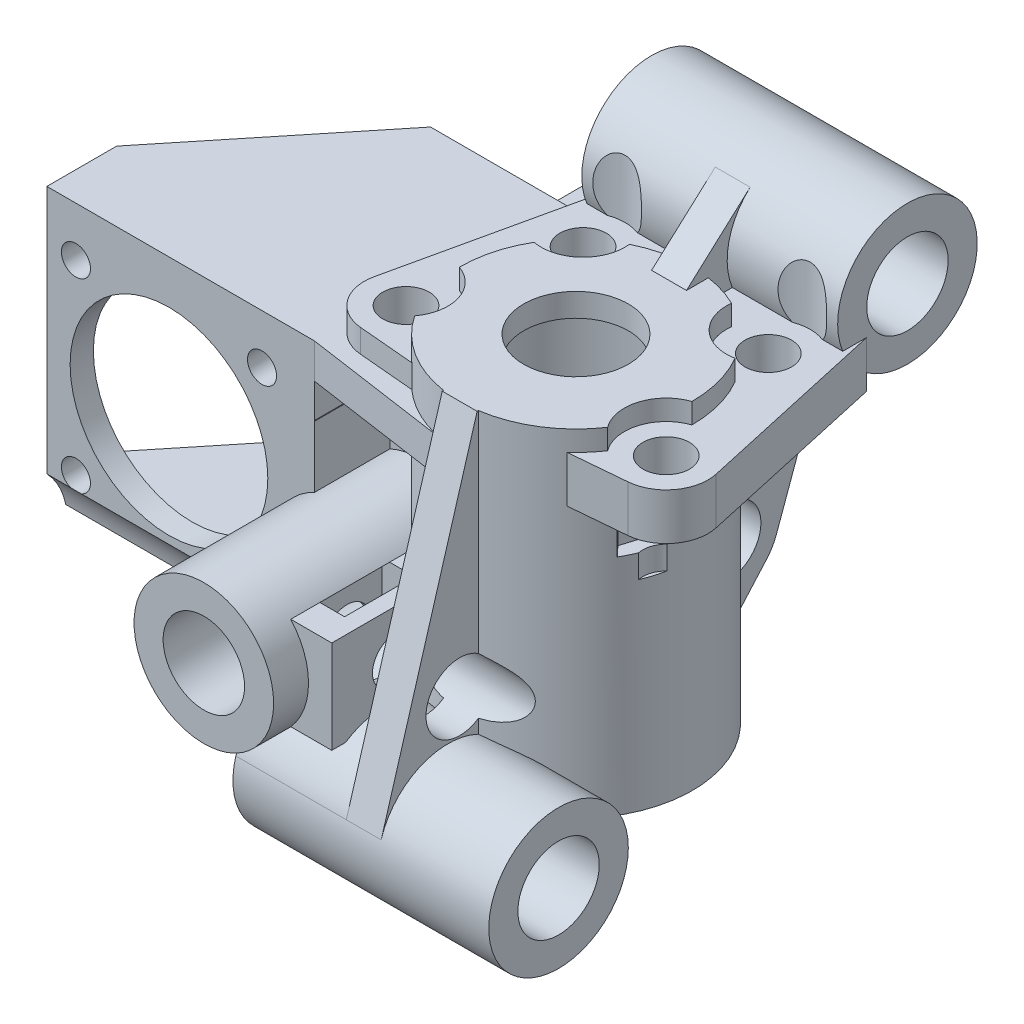
SolidWorks part; units mm, degrees
ref_plane "Front Plane" through (0, 0, 0) normal (0, 0, 1) x (1, 0, 0)
ref_plane "Top Plane" through (0, 0, 0) normal (0, 1, 0) x (1, 0, 0)
ref_plane "Right Plane" through (0, 0, 0) normal (1, 0, 0) x (0, 0, -1)
sketch "Sketch1" plane through (0, 0, 0) normal (0, 0, 1) x (1, 0, 0)
  line L0 (0, 45.2286) -> (0, -45.546) construction
  line L1 (4.5, -14.5) -> (10, -14.5)
  line L2 (10, -14.5) -> (10, 14.5)
  line L7 (10, 14.5) -> (4.5, 14.5)
  line L8 (4.5, 14.5) -> (4.5, 12.5)
  line L9 (4.5, 12.5) -> (8, 12.5)
  line L10 (8, 12.5) -> (8, -12.5)
  line L11 (8, -12.5) -> (4.5, -12.5)
  line L12 (4.5, -12.5) -> (4.5, -14.5)
  line L13 (-9.5385, 0) -> (23.7713, 0) construction
  dimension "D1" = 4.5
  dimension "D2" = 2
  dimension "D3" = 8
  dimension "D4" = 25
  dimension "D5" = 2
revolve "Revolve1" add sketch "Sketch1" angle 360 about L0
ref_axis "Bearing Axis" through (0, -14.5, 0) along (0, 1, 0)
sketch "Sketch3" plane through (0, 0, 0) normal (1, 0, 0) x (0, 0, -1)
  line L0 (6, 14.5) -> (6, -14.5) construction
  line L2 (0, -14.5) -> (0, 14.5) construction
  line L3 (10, 14.5) -> (-10, 14.5) construction
  line L4 (-10, -14.5) -> (10, -14.5) construction
  circle A0 centre (17.5, 15) radius 3.5
  circle A1 centre (17.5, 15) radius 6
  circle A2 centre (-12.5, -15) radius 3.5
  circle A3 centre (-12.5, -15) radius 6
  dimension "D1" = 7
  dimension "D2" = 12
  dimension "D3" = 6
  dimension "D4" = 30
  dimension "D5" = 30
  dimension "D6" = 11.5
  dimension "D7" = 15
extrude "Boss-Extrude2" add sketch "Sketch3" along normal mid plane 22 separate body
sketch "Sketch2" plane through (0, 0, 0) normal (0, 0, 1) x (1, 0, 0)
  circle A0 centre (-12, -6) radius 6
  circle A1 centre (-12, -6) radius 3.5
  dimension "D1" = 7
  dimension "D2" = 12
  dimension "D3" = 12
  dimension "D4" = 6
extrude "Boss-Extrude1" add sketch "Sketch2" along normal blind 20 and the other way blind 15
ref_axis "Smooth Rod Axis" through (-12, -6, -15) along (0, 0, 1)
sketch "Sketch4" plane through (0, 0, 0) normal (0, 1, 0) x (1, 0, 0)
  line L0 (-14.5, -8) -> (-37.5, -8)
  line L1 (-37.5, -8) -> (-37.5, -6)
  line L2 (-37.5, -6) -> (-16.5, -6)
  line L3 (-16.5, -6) -> (-16.5, 19)
  line L4 (-16.5, 19) -> (-14.5, 19)
  line L5 (-14.5, 19) -> (-14.5, -8)
  dimension "D1" = 2
  dimension "D2" = 2
  dimension "D3" = 21
  dimension "D4" = 25
  dimension "D5" = 6
  dimension "D6" = 1
extrude "Boss-Extrude Motor Mount" add sketch "Sketch4" along normal blind 9 and the other way blind 12
sketch "Sketch5" plane through (0, 9, 0) normal (0, 1, 0) x (1, 0, 0)
  line L0 (-14.5, -8) -> (-37.5, -8)
  line L1 (-37.5, -8) -> (-37.5, -6)
  line L2 (-37.5, -6) -> (-37.5, -2)
  line L3 (-37.5, -2) -> (-20.5, 19)
  line L4 (-16.5, 19) -> (-14.5, 19)
  line L6 (-20.5, 19) -> (-16.5, 19)
  line L7 (-14.5, -8) -> (-1.4365, -9.8963)
  line L9 (-14.5, 19) -> (4.682, 8.8362)
  line L11 (-16.5, 19) -> (-16.5, -6) construction
  arc A0 (4.682, 8.8362) -> (-1.4365, -9.8963) centre (0, 0) ccw
  circle A2 centre (0, 0) radius 10 construction
  dimension "D1" = 6
  dimension "D2" = 6
extrude "Boss-Extrude4" add sketch "Sketch5" along normal blind 1.75 and the other way blind 1.25
sketch "Sketch6" plane through (0, -12, 0) normal (0, -1, 0) x (1, 0, 0)
  line L0 (-37.5, 8) -> (-37.5, 2)
  line L1 (-37.5, 2) -> (-24.5476, -14)
  line L2 (-24.5476, -14) -> (-16.5, -14)
  line L3 (-6.9508, -15) -> (-16.5, -15)
  line L4 (-16.5, 8) -> (-37.5, 8)
  line L5 (-20.5, -19) -> (-37.5, 2) construction
  line L6 (-16.5, -15) -> (-16.5, -14)
  line L7 (-16.5, 6) -> (-37.5, 6) construction
  line L8 (-16.5, 8) -> (-1.2502, 9.9215)
  line L9 (-14.5, -15) -> (-6, -15) construction
  line L11 (4.682, -8.8362) -> (-6.9508, -15)
  line L13 (4.682, -8.8362) -> (-14.5, -19) construction
  arc A0 (-1.2502, 9.9215) -> (4.682, -8.8362) centre (0, 0) ccw
  circle A1 centre (0, 0) radius 10 construction
  dimension "D1" = 20
extrude "Boss-Extrude5" add sketch "Sketch6" along normal blind 1.75 and the other way blind 1.25
ref_plane "Flange Plane" through (0, 10.75, 0) normal (0, 1, 0) x (-1, 0, 0)
sketch "Sketch7" plane through (0, 0, 6) normal (0, 0, -1) x (-1, 0, 0)
  line L1 (37.5, 9) -> (16.5, 9)
  line L2 (37.5, 9) -> (37.5, -12)
  line L3 (37.5, -12) -> (16.5, -12)
  line L4 (16.5, 9) -> (16.5, -12)
  line L7 (37.5, 10.75) -> (14.5, 10.75) construction
  line L8 (14.5, 7.75) -> (14.5, -0.5456) construction
  line L9 (37.5, 10.75) -> (37.5, -13.75) construction
  dimension "D1" = 1.75
  dimension "D2" = 2
  dimension "D3" = 21
extrude "Cut-Extrude1" cut sketch "Sketch7" along normal blind 32
sketch "Sketch8" plane through (0, 0, 20) normal (0, 0, 1) x (1, 0, 0)
  circle A0 centre (-12, -6) radius 3.5
  circle A1 centre (-12, -6) radius 3.5 construction
extrude "Cut-Extrude2" cut sketch "Sketch8" against normal through all
sketch "Sketch10" plane through (0, 0, 6) normal (0, 0, -1) x (-1, 0, 0)
  line L0 (27, 9) -> (27, -12) construction
  line L1 (37.5, 9) -> (16.5, 9) construction
  line L2 (16.5, -12) -> (37.5, -12) construction
  line L3 (16.5, -1.5) -> (37.5, -1.5) construction
  line L4 (16.5, 9) -> (16.5, -12) construction
  line L5 (37.5, 9) -> (37.5, -12) construction
  circle A0 centre (27, -1.5) radius 8.5
  circle A1 centre (19, 6.5) radius 1.25
  circle A2 centre (35, 6.5) radius 1.25
  circle A3 centre (35, -9.5) radius 1.25
  circle A4 centre (19, -9.5) radius 1.25
  dimension "D1" = 17
  dimension "D2" = 2.5
  dimension "D3" = 16
  dimension "D4" = 16
sketch "Sketch11" plane through (-11, 0, 0) normal (-1, 0, 0) x (0, 0, 1)
  line L0 (-19, 8.75) -> (-12.9174, 8.75)
  line L1 (-12.9174, 8.75) -> (-12.9174, 10.75)
  line L2 (-19, 10.75) -> (2, 10.75) construction
  line L3 (-19, -12) -> (-19, 9) construction
  line L4 (-19, 8.75) -> (-19, 8.9327)
  arc A0 (-12.9174, 10.75) -> (-19, 8.9327) centre (-17.5, 15) ccw
  circle A1 centre (12.5, -15) radius 6.25
  dimension "D1" = 12.5
sketch "Sketch12" plane through (0, 0, 0) normal (1, 0, 0) x (0, 0, -1)
  circle A0 centre (-12.5, -15) radius 3.5
  circle A1 centre (17.5, 15) radius 3.5
  circle A2 centre (17.5, 15) radius 3.5 construction
  circle A3 centre (-12.5, -15) radius 3.5 construction
extrude "Cut-Extrude7" cut sketch "Sketch10" against normal up to next
extrude "Cut-Extrude8" cut sketch "Sketch11" along normal through all
extrude "Cut-Extrude9" cut sketch "Sketch12" against normal through all and the other way through all
sketch "Sketch13" plane through (0, 0, 0) normal (1, 0, 0) x (0, 0, -1)
  line L0 (-18.2518, -13.2922) -> (-10, 14.5)
  line L1 (-10, 14.5) -> (-8, 14.5)
  line L2 (-8, 14.5) -> (-8, -11.0314)
  line L3 (13.4763, 19.4508) -> (8, 14.5)
  line L4 (8, 14.5) -> (8, -14.5)
  line L5 (8, -14.5) -> (10, -14.5)
  line L6 (10, -14.5) -> (14.8739, -8.9777)
  line L7 (-9.0359, -14.5) -> (10, -14.5) construction
  line L8 (10, 14.5) -> (-10, 14.5) construction
  line L9 (15, -6) -> (-20, -6) construction
  line L10 (15.7317, -7.5305) -> (23.1423, 12.9593)
  arc A0 (23.1423, 12.9593) -> (13.4763, 19.4508) centre (17.5, 15) ccw
  circle A1 centre (17.5, 15) radius 3.5
  arc A2 (-18.2518, -13.2922) -> (-8, -11.0314) centre (-12.5, -15) ccw
  circle A3 centre (-12.5, -15) radius 3.5
  circle A4 centre (-12.5, -15) radius 3.5 construction
  circle A5 centre (17.5, 15) radius 3.5 construction
  circle A6 centre (17.5, 15) radius 6 construction
  circle A7 centre (-12.5, -15) radius 6 construction
  circle A8 centre (11.5, -6) radius 2.9
  circle A9 centre (-11.5, -6) radius 2.9
  arc A10 (14.8739, -8.9777) -> (15.7317, -7.5305) centre (11.5, -6) ccw
  dimension "D3" = 5.8
  dimension "D6" = 4.5
  dimension "D1" = 2
  dimension "D2" = 2
  dimension "D4" = 3.5
  dimension "D5" = 3.5
extrude "Boss-Extrude7" add sketch "Sketch13" along normal mid plane 3
sketch "Sketch21" plane through (0, 0, 0) normal (0, 0, 1) x (1, 0, 0)
  line L0 (-7.5279, -2) -> (-4, -2)
  line L1 (-4, -2) -> (-4, -10)
  line L2 (-4, -10) -> (-7.5279, -10)
  line L3 (-15.1827, -6) -> (-7.4534, -6) construction
  line L4 (-12, -6) -> (-7.6464, -6) construction
  arc A0 (-7.5279, -2) -> (-7.5279, -10) centre (-12, -6) cw
  circle A2 centre (-12, -6) radius 6 construction
  dimension "D1" = 4
  dimension "D3" = 0
extrude "Boss-Extrude10" add sketch "Sketch21" along normal offset from surface 3 and the other way up to surface up to face at (-6, -6, 20) other way up to face at (-11.4093, -9.1994, -15)
sketch "Sketch22" plane through (-4, 0, 0) normal (1, 0, 0) x (0, 0, -1)
  line L0 (-17, -6) -> (15, -6) construction
  line L1 (-17, -10) -> (-17, -2) construction
  circle A0 centre (11.5, -6) radius 2
  circle A1 centre (-11.5, -6) radius 2
  arc A2 (-9.8869, -3.5901) -> (-9.8869, -8.4099) centre (-11.5, -6) ccw construction
  arc A3 (9.8869, -8.4099) -> (9.8869, -3.5901) centre (11.5, -6) ccw construction
  dimension "D1" = 4
extrude "Cut-Extrude15" cut sketch "Sketch22" against normal up to surface and the other way through all up to face at (-13.25, -6, -17)
sketch "Sketch23" plane through (-4, 0, 0) normal (1, 0, 0) x (0, 0, -1)
  circle A0 centre (-11.5, -6) radius 2.9
  circle A1 centre (11.5, -6) radius 2.9
  dimension "D1" = 5.8
extrude "Cut-Extrude16" cut sketch "Sketch23" along normal through all
sketch "Sketch19" plane through (0, 0, 0) normal (0, 0, 1) x (1, 0, 0)
  line L1 (-14.5, 9) -> (-8, 9)
  line L2 (-14.5, 9) -> (-14.5, -2.5)
  line L3 (-14.5, -2.5) -> (-8, -2.5)
  line L4 (-8, 9) -> (-8, -2.5)
  line L6 (-14.5, -3.5505) -> (-14.5, 7.75) construction
  line L7 (-25.424, 9) -> (-16.5, 9) construction
  circle A0 centre (-12, -6) radius 3.5 construction
  point P4 (-8, 12.5)
extrude "Boss-Extrude9" add sketch "Sketch19" along normal mid plane 3
sketch "Sketch15" plane through (0, 10.75, 0) normal (0, 1, 0) x (-1, 0, 0)
  line L0 (0, -19.4967) -> (0, 23.2344) construction
  line L1 (14.7006, 2.6474) -> (11, -14)
  line L2 (11, -14) -> (-11, -14)
  line L4 (-11.5033, 7.0146) -> (-0.7042, 7.9689)
  line L5 (14.5, 8) -> (1.5, 9.8871) construction
  line L8 (11.5033, 7.0146) -> (0.7042, 7.9689)
  line L9 (-11, -14) -> (-14.7006, 2.6474)
  line L10 (-11, -11.5) -> (-11, -23.5) construction
  line L11 (11, -23.5) -> (11, -11.5) construction
  line L13 (11, -14) -> (-11, -14) construction
  line L15 (-11, -14) -> (-11, -21) construction
  circle A0 centre (7.9637, -8.5714) radius 2
  circle A1 centre (11.1864, 3.4286) radius 2
  circle A2 centre (-11.1864, 3.4286) radius 2
  circle A3 centre (-7.9637, -8.5714) radius 2
  arc A4 (-0.7042, 7.9689) -> (0.7042, 7.9689) centre (0, 0) ccw
  circle A5 centre (0, 0) radius 8 construction
  arc A7 (-14.7006, 2.6474) -> (-11.5033, 7.0146) centre (-11.1864, 3.4286) cw
  arc A8 (14.7006, 2.6474) -> (11.5033, 7.0146) centre (11.1864, 3.4286) ccw
  point P29 (-11, -17.5)
  dimension "D1" = 4
  dimension "D4" = 3.6
  dimension "D2" = 11.7
  dimension "D3" = 11.7
  dimension "D5" = 5
  dimension "D6" = 12
extrude "Boss-Extrude Flange" add sketch "Sketch15" along normal mid plane 4
sketch "Sketch14" plane through (0, 0, -15) normal (0, 0, -1) x (-1, 0, 0)
  line L0 (14.5, 0) -> (16.5, 0)
  line L1 (16.5, 0) -> (16.5, -1.3096)
  line L2 (16.5, -10.6904) -> (16.5, -12)
  line L3 (16.5, -12) -> (14.5, -12)
  line L4 (16.5, -12) -> (16.5, 8.75) construction
  line L5 (14.5, -3.5505) -> (14.5, 7.75) construction
  line L6 (14.5, -12) -> (14.5, -8.4495) construction
  arc A0 (14.5, 0) -> (14.5, -12) centre (12, -6) ccw
  arc A1 (16.5, -10.6904) -> (16.5, -1.3096) centre (12, -6) ccw
  dimension "D1" = 13
extrude "Cut-Extrude10" cut sketch "Sketch14" along normal through all
ref_axis "Top Crossbeam Axis" through (11, 15, -17.5) along (-1, 0, 0)
ref_axis "Bottom Crossbeam Axis" through (-11, -15, 12.5) along (1, 0, 0)
sketch "Sketch16" plane through (0, 12.75, 0) normal (0, 1, 0) x (1, 0, 0)
  circle A0 centre (-11.1864, -3.4286) radius 2
  circle A1 centre (-7.9637, 8.5714) radius 2
  circle A2 centre (7.9637, 8.5714) radius 2
  circle A3 centre (11.1864, -3.4286) radius 2
  arc A4 (-9.8007, -1.9864) -> (-9.2305, -3.8467) centre (-11.1864, -3.4286) ccw construction
  arc A5 (-6.0616, 7.9534) -> (-7.487, 6.629) centre (-7.9637, 8.5714) ccw construction
  arc A6 (7.487, 6.629) -> (6.0616, 7.9534) centre (7.9637, 8.5714) ccw construction
  arc A7 (9.2305, -3.8467) -> (9.8007, -1.9864) centre (11.1864, -3.4286) ccw construction
extrude "Cut-Extrude11" cut sketch "Sketch16" against normal blind 10 and the other way through all
sketch "Sketch17" plane through (0, 8.75, 0) normal (0, -1, 0) x (1, 0, 0)
  line L0 (-11.1864, 3.4286) -> (0, 0) construction
  line L1 (8.8256, 0.8935) -> (12.2015, 0.1166)
  line L2 (12.2015, 0.1166) -> (14.5622, 2.6517)
  line L3 (14.5622, 2.6517) -> (13.5471, 5.9637)
  line L4 (13.5471, 5.9637) -> (10.1712, 6.7406)
  line L5 (10.1712, 6.7406) -> (7.8105, 4.2055)
  line L6 (7.8105, 4.2055) -> (8.8256, 0.8935)
  line L7 (4.6529, -7.5525) -> (5.4259, -10.9293)
  line L8 (5.4259, -10.9293) -> (8.7368, -11.9481)
  line L9 (8.7368, -11.9481) -> (11.2746, -9.5903)
  line L10 (11.2746, -9.5903) -> (10.5015, -6.2135)
  line L11 (10.5015, -6.2135) -> (7.1907, -5.1947)
  line L12 (7.1907, -5.1947) -> (4.6529, -7.5525)
  line L13 (-8.7368, -11.9481) -> (-5.4259, -10.9293)
  line L14 (-5.4259, -10.9293) -> (-4.6529, -7.5525)
  line L15 (-4.6529, -7.5525) -> (-7.1907, -5.1947)
  line L16 (-7.1907, -5.1947) -> (-10.5015, -6.2135)
  line L17 (-10.5015, -6.2135) -> (-11.2746, -9.5903)
  line L18 (-11.2746, -9.5903) -> (-8.7368, -11.9481)
  line L19 (-14.5622, 2.6517) -> (-12.2015, 0.1166)
  line L20 (-12.2015, 0.1166) -> (-8.8256, 0.8935)
  line L21 (-8.8256, 0.8935) -> (-7.8105, 4.2055)
  line L22 (-7.8105, 4.2055) -> (-10.1712, 6.7406)
  line L23 (-10.1712, 6.7406) -> (-13.5471, 5.9637)
  line L24 (-13.5471, 5.9637) -> (-14.5622, 2.6517)
  line L25 (0, 0) -> (-7.9637, -8.5714) construction
  line L26 (0, 0) -> (7.9637, -8.5714) construction
  line L27 (0, 0) -> (11.1864, 3.4286) construction
  circle A0 centre (11.1864, 3.4286) radius 3 construction
  circle A1 centre (7.9637, -8.5714) radius 3 construction
  circle A2 centre (-7.9637, -8.5714) radius 3 construction
  circle A3 centre (-11.1864, 3.4286) radius 3 construction
  arc A4 (6.0616, -7.9534) -> (7.487, -6.629) centre (7.9637, -8.5714) ccw construction
  dimension "D1" = 6
extrude "Cut-Extrude12" cut sketch "Sketch17" against normal blind 1 and the other way blind 4
sketch "Sketch18" plane through (0, 12.75, 0) normal (0, 1, 0) x (1, 0, 0)
  circle A0 centre (-7.9637, 8.5714) radius 3.6
  circle A1 centre (-11.1864, -3.4286) radius 3.6
  circle A2 centre (11.1864, -3.4286) radius 3.6
  circle A3 centre (7.9637, 8.5714) radius 3.6
  arc A5 (11.5033, -7.0146) -> (14.7006, -2.6474) centre (11.1864, -3.4286) ccw construction
  arc A7 (-14.7006, -2.6474) -> (-11.5033, -7.0146) centre (-11.1864, -3.4286) ccw construction
  arc A10 (-6.0616, 7.9534) -> (-7.487, 6.629) centre (-7.9637, 8.5714) ccw construction
  arc A11 (7.487, 6.629) -> (6.0616, 7.9534) centre (7.9637, 8.5714) ccw construction
extrude "Cut-Extrude13" cut sketch "Sketch18" along normal through all
sketch "Sketch20" plane through (0, 7.75, 0) normal (0, -1, 0) x (1, 0, 0)
  line L0 (-14.5622, 7.991) -> (-14.5622, 2.6517)
  line L1 (-14.5622, 2.6517) -> (-7.8105, 4.2055)
  line L2 (-7.8105, 4.2055) -> (-7.8105, 8.971)
  line L3 (-14.5, 8) -> (-1.5, 9.8871) construction
  line L4 (-7.8105, 8.971) -> (-14.5622, 7.991)
extrude "Cut-Extrude14" cut sketch "Sketch20" along normal blind 3
sketch "Sketch24" plane through (0, 0, 0) normal (0, 0, 1) x (1, 0, 0)
  line L0 (4.5, 14.5) -> (4.5, 12.5)
  line L1 (4.5, 12.5) -> (8, 12.5)
  line L4 (8, 12.5) -> (8, -12.5)
  line L7 (8, -12.5) -> (4.5, -12.5)
  line L8 (4.5, -12.5) -> (4.5, -14.5)
  line L13 (4.5, -14.5) -> (0, -14.5)
  line L14 (0, -14.5) -> (0, 14.5)
  line L15 (0, 14.5) -> (4.5, 14.5)
revolve "Cut-Revolve1" cut sketch "Sketch24" angle 360 about axis through (0, -14.5, 0) along (0, 1, 0)
ref_plane "Smooth Rod Nut Plane" through (-6.8, 0, 0) normal (1, 0, 0) x (0, 0, -1)
sketch "Sketch25" plane through (-6.8, 0, 0) normal (1, 0, 0) x (0, 0, -1)
  line L0 (15, -6) -> (-20, -6) construction
  line L1 (8.0359, -6) -> (9.7679, -9)
  line L2 (9.7679, -9) -> (15, -9)
  line L3 (15, -2) -> (15, -10) construction
  line L4 (-8.5, -2) -> (-14.5, -2)
  line L5 (15, -3) -> (9.7679, -3)
  line L6 (9.7679, -3) -> (8.0359, -6)
  line L7 (-17, -2) -> (-9.1652, -2) construction
  line L9 (-14.5, -2) -> (-14.5, -7.7321)
  line L10 (-14.5, -7.7321) -> (-11.5, -9.4641)
  line L11 (-11.5, -9.4641) -> (-8.5, -7.7321)
  line L12 (-8.5, -7.7321) -> (-8.5, -2)
  line L14 (15, -3) -> (15, -9)
  line L17 (15.1969, -6.4032) -> (13.4648, -3.4032) [skipped]
  line L18 (13.4648, -8.5968) -> (15.1969, -5.5968) [skipped]
  line L19 (-10.8579, -2.1652) -> (-13.8579, -3.8972) [skipped]
  line L20 (-7.8579, -4.6387) -> (-10.8579, -2.9066) [skipped]
  circle A0 centre (11.5, -6) radius 3 construction
  circle A1 centre (-11.5, -6) radius 3 construction
  circle A2 centre (11.5, -6) radius 2 construction
  circle A3 centre (-11.5, -6) radius 2 construction
  dimension "D1" = 6
extrude "Cut-Extrude17" cut sketch "Sketch25" against normal mid plane 2.8
split "Split1" [suppressed] bodies to split 131
